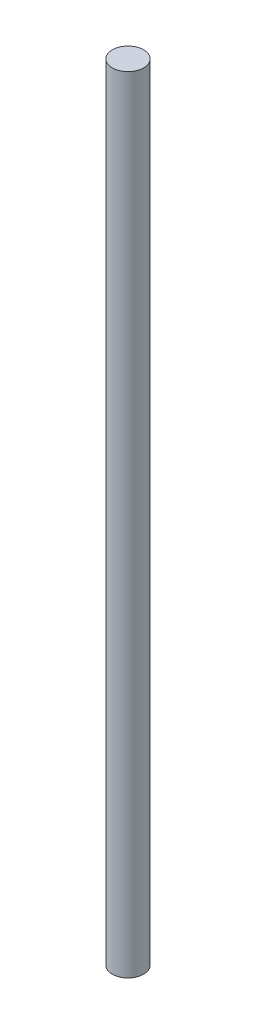
SolidWorks part; units mm, degrees
ref_plane "前视基准面" through (0, 0, 0) normal (0, 0, 1) x (1, 0, 0)
ref_plane "上视基准面" through (0, 0, 0) normal (0, 1, 0) x (1, 0, 0)
ref_plane "右视基准面" through (0, 0, 0) normal (1, 0, 0) x (0, 0, -1)
other "Configuration Table"
sketch "草图1" plane through (0, 0, 0) normal (0, 1, 0) x (1, 0, 0)
  circle A0 centre (0, 0) radius 6
extrude "凸台-拉伸1" add sketch "草图1" along normal blind 300
